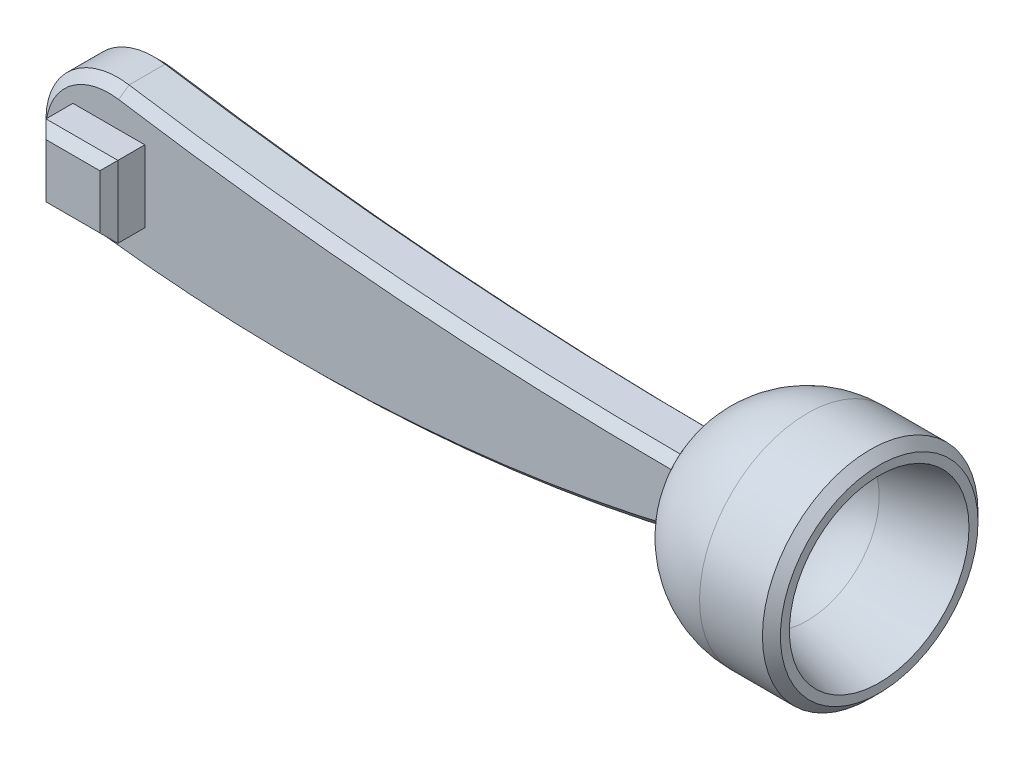
SolidWorks part; units mm, degrees
ref_plane "Front Plane" through (0, 0, 0) normal (0, 0, 1) x (1, 0, 0)
ref_plane "Top Plane" through (0, 0, 0) normal (0, 1, 0) x (1, 0, 0)
ref_plane "Right Plane" through (0, 0, 0) normal (1, 0, 0) x (0, 0, -1)
sketch "Sketch2" plane through (0, 0, 0) normal (0, 0, 1) x (1, 0, 0)
  line L0 (-85, 0) -> (85, 0) construction
  circle A0 centre (-85, 0) radius 20
  circle A1 centre (85, 0) radius 7.5
  arc A2 (-81.8718, 19.7538) -> (84.9221, 7.4996) centre (74.5404, 1007.4457) ccw
  arc A3 (-87.4615, -19.8479) -> (86.9844, -7.2327) centre (-32.0772, 426.7308) ccw
  point P4 (0, 0)
  dimension "D2" = 40
  dimension "D3" = 15
  dimension "D4" = 450
  dimension "D5" = 1000
  dimension "D1" = 170
extrude "Boss-Extrude1" add sketch "Sketch2" along normal mid plane 15 contours A0 L0 A1 A2 | L0 A0 A3 A1 | A0 | A1 region at (-6.4445, 6.0296, 0) region at (-72.1313, -14.5633, 0) region at (-3.1113, -10.4688, 0) region at (79.82, 5.1265, 0)
chamfer "Chamfer1" distance 2.5 angle 45 8 edges at (92.4276, 1.0397, -7.5) (1.2686, 10.1337, -7.5) (-104.8037, 2.7953, -7.5) (0.3802, -22.0971, -7.5) (-104.8037, 2.7953, 7.5) (1.2686, 10.1337, 7.5) (92.4276, 1.0397, 7.5) (0.3802, -22.0971, 7.5)
sketch "Sketch3" plane through (0, 0, 7.5) normal (0, 0, 1) x (1, 0, 0)
  line L1 (-95, 10) -> (-75, 10)
  line L2 (-95, 10) -> (-95, -10)
  line L3 (-95, -10) -> (-75, -10)
  line L4 (-75, 10) -> (-75, -10)
  line L5 (-95, 10) -> (-75, -10) construction
  line L6 (-95, -10) -> (-75, 10) construction
  arc A0 (-81.8718, 19.7538) -> (-87.4615, -19.8479) centre (-85, 0) ccw construction
  point P0 (-85, 0)
  dimension "D1" = 20
  dimension "D2" = 20
  dimension "D3" = 0
extrude "Boss-Extrude2" add sketch "Sketch3" along normal blind 10
chamfer "Chamfer4" distance 2.5 angle 45 4 edges at (-85, 10, 17.5) (-95, 0, 17.5) (-85, -10, 17.5) (-75, 0, 17.5)
sketch "Sketch6" plane through (0, 0, -7.5) normal (0, 0, -1) x (-1, 0, 0)
  circle A0 centre (85, 0) radius 5
extrude "Boss-Extrude3" add sketch "Sketch6" along normal blind 10
sketch "Sketch7" plane through (0, 0, 0) normal (0, 1, 0) x (1, 0, 0)
  line L0 (-136.3063, 0) -> (179.0767, 0) construction
  line L1 (101.9143, 30) -> (101.9143, 20)
  line L2 (101.9143, -30) -> (101.9143, -20)
  line L3 (101.9143, 20) -> (101.9143, -20)
  arc A0 (101.9143, 20) -> (101.9143, -20) centre (101.9143, 0) ccw
  arc A1 (101.9143, 30) -> (101.9143, -30) centre (101.9143, 0) ccw
  dimension "D2" = 20
  dimension "D1" = 0
  dimension "D3" = 40
  dimension "D4" = 10
extrude "Cut-Extrude3" cut sketch "Sketch7" against normal mid plane 34 contours L0 A0 L3 | A0 L0 L3 region at (93.426, 0, -8.4883) region at (93.426, 0, 8.4883)
revolve "Revolve2" add sketch "Sketch7<5>" angle 360 about L0 region at (85.7866, 0, 16.1277)
sketch "Sketch7<5>" plane through (0, 0, 0) normal (0, 1, 0) x (1, 0, 0) same geometry as "Sketch7"
sketch "Sketch11" plane through (101.9143, 0, 0) normal (1, 0, 0) x (0, 0, -1)
  circle A0 centre (0, 0) radius 20
  circle A1 centre (0, 0) radius 30
extrude "Boss-Extrude4" add sketch "Sketch11" along normal blind 20
chamfer "Chamfer5" distance 5 distance2 20 1 edges at (121.9143, 0, -20) first distance on face at (121.9143, 0, -30)
chamfer "Chamfer6" distance 2.5 angle 45 1 edges at (121.9143, 0, -30)
